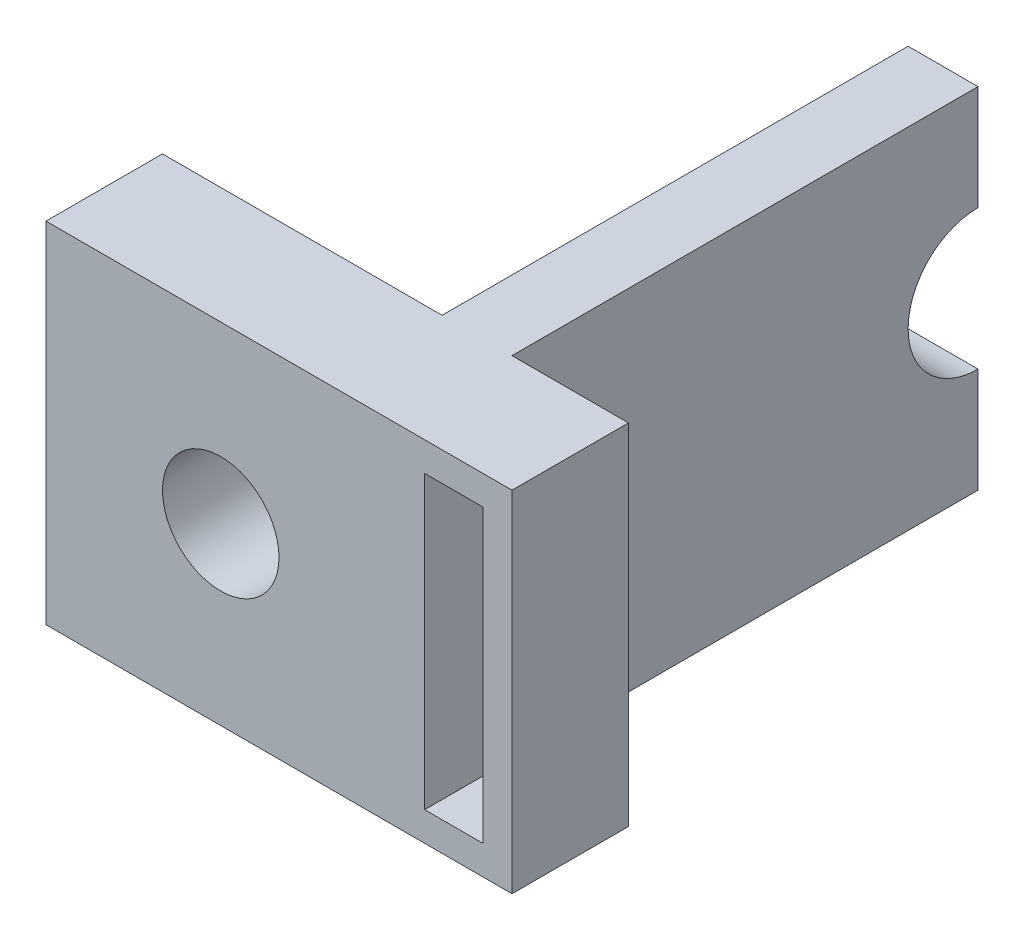
SolidWorks part; units mm, degrees
ref_plane "Front Plane" through (0, 0, 0) normal (0, 0, 1) x (1, 0, 0)
ref_plane "Top Plane" through (0, 0, 0) normal (0, 1, 0) x (1, 0, 0)
ref_plane "Right Plane" through (0, 0, 0) normal (1, 0, 0) x (0, 0, -1)
sketch "Sketch1" plane through (0, 0, 0) normal (0, 0, 1) x (1, 0, 0)
  line L1 (0, 0) -> (20, 0)
  line L2 (0, 0) -> (0, 15)
  line L3 (0, 15) -> (20, 15)
  line L4 (20, 0) -> (20, 15)
  dimension "D1" = 20
  dimension "D2" = 15
extrude "Boss-Extrude1" add sketch "Sketch1" along normal blind 5 contours L2 L3 L4 L1
sketch "Sketch2" plane through (0, 0, 5) normal (0, 0, 1) x (1, 0, 0)
  line L0 (0, 0) -> (0, 15) construction
  circle A0 centre (7.5, 7.5) radius 2.5
  point P4 (0, 7.5)
  point P5 (0, 0)
  dimension "D1" = 5
  dimension "D2" = 7.5
extrude "Cut-Extrude1" cut sketch "Sketch2" against normal blind 5
sketch "Sketch3" plane through (0, 0, 0) normal (0, 0, -1) x (-1, 0, 0)
  line L1 (0, 15) -> (-5, 15)
  line L5 (0, 15) -> (-20, 15) construction
  line L6 (-12, 15) -> (-15, 15)
  line L7 (-12, 15) -> (-12, 0)
  line L8 (-12, 0) -> (-15, 0)
  line L9 (-15, 15) -> (-15, 0)
  line L10 (0, 0) -> (-20, 0) construction
  line L11 (-20, 0) -> (-20, 15) construction
  point P11 (-16.0676, 0)
  dimension "D1" = 3
  dimension "D2" = 5
extrude "Boss-Extrude2" add sketch "Sketch3" along normal blind 20 contours L9 L8 L7 L6
sketch "Sketch4" plane through (15, 0, 0) normal (1, 0, 0) x (0, 0, -1)
  line L0 (20, 15) -> (20, 0) construction
  line L1 (20, 15) -> (20, 7.5) construction
  line L2 (20, 7.5) -> (20, 0) construction
  arc A0 (20, 10.5) -> (20, 4.5) centre (20, 7.5) ccw
  dimension "D1" = 3
extrude "Cut-Extrude2" cut sketch "Sketch4" against normal through all and the other way through all
sketch "Sketch5" plane through (0, 0, 0) normal (0, 0, -1) x (-1, 0, 0)
  line L0 (-20, 0) -> (-20, 15) construction
  line L1 (-16.25, 13.75) -> (-18.75, 13.75)
  line L2 (-16.25, 13.75) -> (-16.25, 1.25)
  line L3 (-16.25, 1.25) -> (-18.75, 1.25)
  line L4 (-18.75, 13.75) -> (-18.75, 1.25)
  line L5 (-15, 15) -> (-20, 15) construction
  point P6 (-20, 7.5)
  point P7 (-18.75, 7.5)
  point P10 (-17.5, 15)
  point P11 (-17.5, 13.75)
  dimension "D1" = 12.5
  dimension "D2" = 2.5
extrude "Cut-Extrude3" cut sketch "Sketch5" against normal through all
